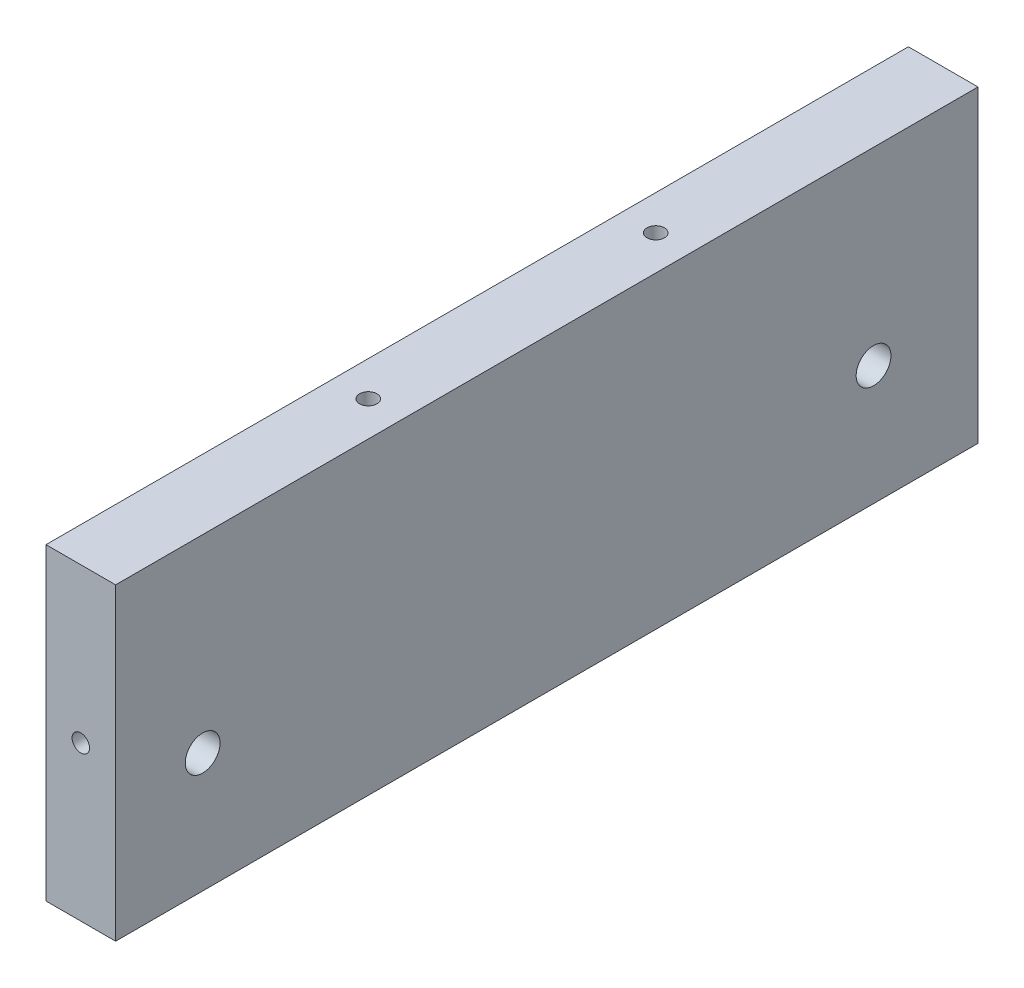
SolidWorks part; units mm, degrees
material "Beech"
ref_plane "Front Plane" through (0, 0, 0) normal (0, 0, 1) x (1, 0, 0)
ref_plane "Top Plane" through (0, 0, 0) normal (0, 1, 0) x (1, 0, 0)
ref_plane "Right Plane" through (0, 0, 0) normal (1, 0, 0) x (0, 0, -1)
sketch "Sketch1" plane through (0, 0, 0) normal (0, 0, 1) x (1, 0, 0)
  line L0 (-16.7045, 12.7) -> (-231.3045, 12.7) construction
  line L1 (-244.0045, 69) -> (-231.3045, 69)
  line L2 (-244.0045, 69) -> (-244.0045, 12.7)
  line L3 (-244.0045, 12.7) -> (-231.3045, 12.7)
  line L4 (-231.3045, 69) -> (-231.3045, 12.7)
  dimension "D1" = 12.7
extrude "Boss-Extrude1" add sketch "Sketch1" along normal up to surface (157.3 mm away)
hole_wizard "Hole1" positions "Sketch2" profile "Sketch3" legacy
sketch "Sketch2" plane through (-124.0045, 0, 2.2757) normal (0, -1, 0) x (1, 0, 0)
  line L1 (0, 465.9538) -> (0, 167.7243) construction
  point P1 (113.65, 128.8076)
  point P3 (113.65, 23.941)
  point P5 (-94.6, 161.3743)
  point P7 (94.6, 161.3743)
  point P9 (0, 161.3743)
  point P11 (0, 193.1243)
  point P13 (0, 440.5538)
  point P15 (0, 301.9704)
  point P17 (40.9792, 301.9704)
  point P19 (166.7958, 301.9704)
  point P21 (207.775, 440.5538)
  point P23 (207.775, 333.0214)
  point P25 (207.775, 225.489)
  point P27 (207.775, 137.4243)
  point P29 (207.775, 10.4243)
  point P33 (-207.775, 10.4243)
  point P34 (-207.775, 137.4243)
  point P35 (-207.775, 225.489)
  point P36 (-207.775, 333.0214)
  point P37 (-207.775, 440.5538)
  point P38 (-166.7958, 301.9704)
  point P39 (-40.9792, 301.9704)
  point P40 (-113.65, 23.941)
  point P41 (-113.65, 128.8076)
sketch "Sketch3" plane through (-10.3545, 0, 131.0833) normal (1, 0, 0) x (0, 0, -1)
  line L0 (0, 0) -> (0, 32.7039)
  line L1 (0, 32.7039) -> (1.5875, 31.75)
  line L2 (1.5875, 31.75) -> (1.5875, 4.0177)
  line L3 (1.5875, 4.0177) -> (5.08, 0)
  line L4 (5.08, 0) -> (0, 0)
  line L5 (0, -14.3089) -> (0, 102.4216) construction
  line L6 (0, 32.7039) -> (-1.5875, 31.75) construction
  line L7 (-1.5875, 4.0177) -> (-5.08, 0) construction
  dimension "Diameter" = 3.175
  dimension "Depth" = 31.75
  dimension "C-Sink Diameter" = 10.16
  dimension "C-Sink Angle" = 82
  dimension "Drill Angle" = 118
hole_wizard "Hole2" positions "Sketch4" profile "Sketch5" legacy
sketch "Sketch4" plane through (-124.0045, 0, 155.0243) normal (0, -1, 0) x (-1, 0, 0)
  line L1 (0, 465.9538) -> (0, 167.7243) construction
  point P1 (113.65, 128.8076)
  point P3 (113.65, 23.941)
  point P5 (-94.6, 161.3743)
  point P7 (94.6, 161.3743)
  point P9 (0, 161.3743)
  point P11 (0, 193.1243)
  point P13 (0, 440.5538)
  point P15 (0, 301.9704)
  point P17 (40.9792, 301.9704)
  point P19 (166.7958, 301.9704)
  point P21 (207.775, 440.5538)
  point P23 (207.775, 333.0214)
  point P25 (207.775, 225.489)
  point P27 (207.775, 137.4243)
  point P29 (207.775, 10.4243)
  point P33 (-207.775, 10.4243)
  point P34 (-207.775, 137.4243)
  point P35 (-207.775, 225.489)
  point P36 (-207.775, 333.0214)
  point P37 (-207.775, 440.5538)
  point P38 (-166.7958, 301.9704)
  point P39 (-40.9792, 301.9704)
  point P40 (-113.65, 23.941)
  point P41 (-113.65, 128.8076)
sketch "Sketch5" plane through (-237.6545, 0, 26.2167) normal (1, 0, 0) x (0, 0, -1)
  line L0 (0, 0) -> (0, 32.7039)
  line L1 (0, 32.7039) -> (1.5875, 31.75)
  line L2 (1.5875, 31.75) -> (1.5875, 4.0177)
  line L3 (1.5875, 4.0177) -> (5.08, 0)
  line L4 (5.08, 0) -> (0, 0)
  line L5 (0, -14.3089) -> (0, 102.4216) construction
  line L6 (0, 32.7039) -> (-1.5875, 31.75) construction
  line L7 (-1.5875, 4.0177) -> (-5.08, 0) construction
  dimension "Diameter" = 3.175
  dimension "Depth" = 31.75
  dimension "C-Sink Diameter" = 10.16
  dimension "C-Sink Angle" = 82
  dimension "Drill Angle" = 118
hole_wizard "Hole" positions "Sketch6" profile "Sketch7" legacy
sketch "Sketch6" plane through (-124.0045, 277.2867, 170) normal (0, 0, 1) x (-1, 0, 0)
  point P0 (113.65, 236.4367)
  point P2 (207.775, 236.4367)
sketch "Sketch7" plane through (-237.6545, 40.85, 170) normal (1, 0, 0) x (0, -1, 0)
  line L0 (0, 0) -> (0, 32.7039)
  line L1 (0, 32.7039) -> (1.5875, 31.75)
  line L2 (1.5875, 31.75) -> (1.5875, 4.0177)
  line L3 (1.5875, 4.0177) -> (5.08, 0)
  line L4 (5.08, 0) -> (0, 0)
  line L5 (0, -14.3089) -> (0, 102.4216) construction
  line L6 (0, 32.7039) -> (-1.5875, 31.75) construction
  line L7 (-1.5875, 4.0177) -> (-5.08, 0) construction
  dimension "Diameter" = 3.175
  dimension "Depth" = 31.75
  dimension "C-Sink Diameter" = 10.16
  dimension "C-Sink Angle" = 82
  dimension "Drill Angle" = 118
hole_wizard "Hole3" positions "Sketch8" profile "Sketch9" legacy
sketch "Sketch8" plane through (-124.0045, 88.05, 155.0243) normal (0, 1, 0) x (1, 0, 0)
  point P15 (-162.3, -8.6257)
  point P34 (-113.65, 50.1576)
  point P36 (-113.65, 102.591)
  point P54 (162.3, -8.6257)
  point P55 (113.65, 50.1576)
  point P56 (113.65, 102.591)
  point P71 (63.85, 161.3743)
  point P73 (0, 161.3743)
  point P74 (-63.85, 161.3743)
sketch "Sketch9" plane through (-286.3045, 88.05, 163.65) normal (1, 0, 0) x (0, 0, 1)
  line L0 (0, 0) -> (0, 32.7039)
  line L1 (0, 32.7039) -> (1.5875, 31.75)
  line L2 (1.5875, 31.75) -> (1.5875, 4.0177)
  line L3 (1.5875, 4.0177) -> (5.08, 0)
  line L4 (5.08, 0) -> (0, 0)
  line L5 (0, -14.3089) -> (0, 102.4216) construction
  line L6 (0, 32.7039) -> (-1.5875, 31.75) construction
  line L7 (-1.5875, 4.0177) -> (-5.08, 0) construction
  dimension "Diameter" = 3.175
  dimension "Depth" = 31.75
  dimension "C-Sink Diameter" = 10.16
  dimension "C-Sink Angle" = 82
  dimension "Drill Angle" = 118
hole_wizard "Hole4" positions "Sketch10" profile "Sketch11" legacy
sketch "Sketch10" plane through (-124.0045, 88.05, 2.2757) normal (0, 1, 0) x (-1, 0, 0)
  point P15 (-162.3, -8.6257)
  point P34 (-113.65, 50.1576)
  point P36 (-113.65, 102.591)
  point P54 (162.3, -8.6257)
  point P55 (113.65, 50.1576)
  point P56 (113.65, 102.591)
  point P71 (63.85, 161.3743)
  point P73 (0, 161.3743)
  point P74 (-63.85, 161.3743)
sketch "Sketch11" plane through (38.2955, 88.05, -6.35) normal (1, 0, 0) x (0, 0, 1)
  line L0 (0, 0) -> (0, 32.7039)
  line L1 (0, 32.7039) -> (1.5875, 31.75)
  line L2 (1.5875, 31.75) -> (1.5875, 4.0177)
  line L3 (1.5875, 4.0177) -> (5.08, 0)
  line L4 (5.08, 0) -> (0, 0)
  line L5 (0, -14.3089) -> (0, 102.4216) construction
  line L6 (0, 32.7039) -> (-1.5875, 31.75) construction
  line L7 (-1.5875, 4.0177) -> (-5.08, 0) construction
  dimension "Diameter" = 3.175
  dimension "Depth" = 31.75
  dimension "C-Sink Diameter" = 10.16
  dimension "C-Sink Angle" = 82
  dimension "Drill Angle" = 118
hole_wizard "1/4 (0.25) Diameter Hole1" positions "Sketch12" profile "Sketch13" hole size "1/4" standard "ANSI Inch" end condition through all
sketch "Sketch12" plane through (-244.0045, 0, 0) normal (-1, 0, 0) x (0, 0, 1)
  point P0 (141.425, 34.5)
  point P2 (19.05, 34.5)
sketch "Sketch13" plane through (-244.0045, 34.5, 141.425) normal (0, 1, 0) x (0, 0, 1)
  line L0 (0, 0) -> (0, 12.7)
  line L1 (0, 12.7) -> (3.175, 12.7)
  line L2 (3.175, 12.7) -> (3.175, 0)
  line L5 (3.175, 0) -> (0, 0)
  line L11 (0, -6.35) -> (0, 107.95) construction
  dimension "Thru Hole Dia." = 6.35
  dimension "Thru Hole Depth" = 12.7
